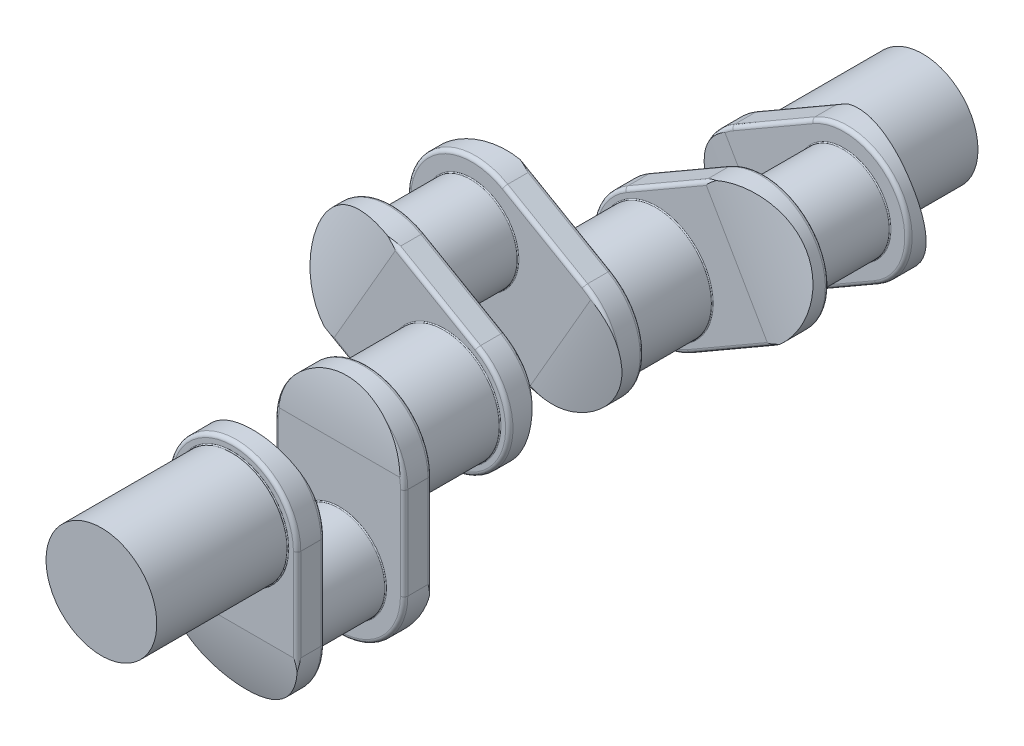
SolidWorks part; units mm, degrees
ref_plane "Front Plane" through (0, 0, 0) normal (0, 0, 1) x (1, 0, 0)
ref_plane "Top Plane" through (0, 0, 0) normal (0, 1, 0) x (1, 0, 0)
ref_plane "Right Plane" through (0, 0, 0) normal (1, 0, 0) x (0, 0, -1)
sketch "Sketch1" plane through (0, 0, 0) normal (0, 0, 1) x (1, 0, 0)
  circle A0 centre (0, 0) radius 31.75
  dimension "D1" = 63.5
extrude "Boss-Extrude1" add sketch "Sketch1" along normal blind 27.31
sketch "Sketch2" plane through (0, 0, 27.31) normal (0, 0, 1) x (1, 0, 0)
  line L0 (44.45, 63.5) -> (44.45, 0)
  line L1 (-44.45, 63.5) -> (-44.45, 0)
  arc A0 (-44.45, 0) -> (44.45, 0) centre (0, 0) ccw
  arc A1 (44.45, 63.5) -> (-44.45, 63.5) centre (0, 63.5) ccw
  circle A2 centre (0, 0) radius 31.75 construction
  dimension "D1" = 12.7
  dimension "D2" = 88.9
  dimension "D3" = 63.5
extrude "Boss-Extrude2" add sketch "Sketch2" along normal blind 19
sketch "Sketch3" plane through (0, 0, 46.31) normal (0, 0, 1) x (1, 0, 0)
  circle A0 centre (0, 63.5) radius 38.1
  dimension "D1" = 76.2
extrude "Boss-Extrude3" add sketch "Sketch3" along normal blind 26.67
sketch "Sketch4" plane through (0, 0, 0) normal (1, 0, 0) x (0, 0, -1)
  line L0 (-46.31, 0) -> (-27.31, 0) construction
  line L1 (-46.31, 0) -> (-46.31, -44.45) construction
  line L2 (-46.31, -44.45) -> (-27.31, -44.45) construction
  line L3 (-46.31, 0) -> (-60.4648, 0)
  line L4 (-60.4648, 0) -> (-60.4648, -44.45)
  line L5 (-60.4648, -44.45) -> (-36.81, -44.45)
  line L6 (-46.31, 63.5) -> (-27.31, 63.5) construction
  line L7 (-27.31, 107.95) -> (-46.31, 107.95) construction
  line L8 (-27.31, 63.5) -> (-27.31, 107.95) construction
  line L9 (-27.31, 63.5) -> (-17.3681, 63.5)
  line L10 (-17.3681, 63.5) -> (-17.3681, 107.95)
  line L11 (-17.3681, 107.95) -> (-32.31, 107.95)
  arc A0 (-46.31, 0) -> (-36.81, -44.45) centre (122.2064, 12.7757) ccw
  arc A1 (-27.31, 63.5) -> (-32.31, 107.95) centre (-196.2738, 67.0002) ccw
  dimension "D1" = 169
  dimension "D3" = 169
  dimension "D2" = 5
extrude "Cut-Extrude1" cut sketch "Sketch4" against normal through all both and the other way through all
fillet "Fillet1" radius 0.64 2 edges at (31.75, 0, 27.31) (38.1, 63.5, 46.31)
fillet "Fillet2" radius 2.54 8 edges at (-44.45, 31.75, 46.31) (0, 107.95, 46.31) (-44.3111, 67.0111, 27.31) (-44.45, 31.75, 27.31) (0, -44.45, 27.31) (44.3111, 67.0111, 27.31) (44.45, 31.75, 46.31) (44.45, 31.75, 27.31)
mirror "Mirror2" about plane through (0, 0, 0) normal (0, 0, 1) of "Fillet2", "Fillet1", "Cut-Extrude1", "Boss-Extrude3", "Boss-Extrude2", "Boss-Extrude1"
pattern_linear "LPattern1" count 3 spacing 145.96 along (0, 0, -1) of bodies 117
ref_axis "Axis1" through (0, 63.5, 166.4472) along (0, 0, -1)
move or copy body "Body-Move/Copy1" bodies to move or copy 118 copy no rotation origin (0, 63.5, 0) rotation axis (0, 0, -1) rotation angle 120
move or copy body "Body-Move/Copy2" bodies to move or copy 119 copy no rotation origin (0, 63.5, 0) rotation axis (0, 0, 1) rotation angle 120
combine bodies "Combine1" operation type add bodies to combine 117 120 121
sketch "Sketch5" plane through (0, 0, 72.98) normal (0, 0, 1) x (1, 0, 0)
  circle A1 centre (0, 63.5) radius 38.1
  circle A2 centre (0, 63.5) radius 38.1
  dimension "D1" = 0
extrude "Boss-Extrude4" add sketch "Sketch5" along normal blind 63.5
sketch "Sketch6" plane through (0, 0, -364.9) normal (0, 0, -1) x (-1, 0, 0)
  circle A1 centre (0, 63.5) radius 38.1
  circle A2 centre (0, 63.5) radius 38.1
  dimension "D1" = 0
extrude "Boss-Extrude5" add sketch "Sketch6" along normal blind 63.5
